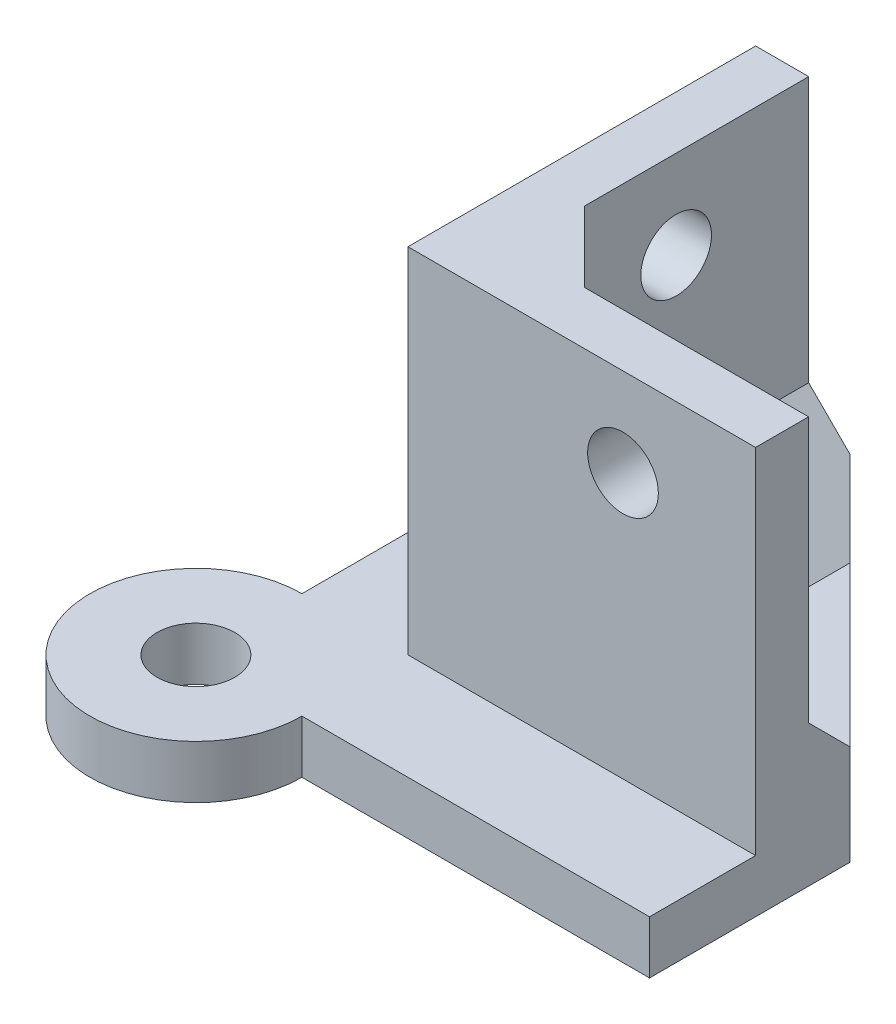
SolidWorks part; units mm, degrees
ref_plane "前视" through (0, 0, 0) normal (0, 0, 1) x (1, 0, 0)
ref_plane "上视" through (0, 0, 0) normal (0, 1, 0) x (1, 0, 0)
ref_plane "右视" through (0, 0, 0) normal (1, 0, 0) x (0, 0, -1)
sketch "Sketch1" plane through (0, 0, 0) normal (0, 1, 0) x (1, 0, 0)
  line L0 (0, 0) -> (0, 19)
  line L1 (0, 0) -> (19, 0)
  line L2 (19, 0) -> (0, 19)
  dimension "D1" = 19
  dimension "D2" = 19
extrude "Boss-Extrude1" add sketch "Sketch1" along normal blind 5
sketch "Sketch2" plane through (0, 5, 0) normal (0, 1, 0) x (1, 0, 0)
  line L0 (0, 19) -> (0, 0)
  line L1 (0, 0) -> (19, 0)
  line L2 (19, 0) -> (16, 3)
  line L3 (19, 0) -> (0, 19) construction
  line L4 (16, 3) -> (3, 3)
  line L5 (3, 3) -> (3, 16)
  line L6 (3, 16) -> (0, 19)
  dimension "D1" = 3
  dimension "D2" = 3
extrude "Boss-Extrude2" add sketch "Sketch2" along normal blind 15
sketch "Sketch3" plane through (0, 0, 0) normal (0, 0, 1) x (1, 0, 0)
  line L0 (0, 20) -> (0, 0) construction
  line L1 (0, 0) -> (19, 0) construction
  circle A0 centre (11.5, 15) radius 2
  dimension "D1" = 11.5
  dimension "D2" = 15
extrude "Cut-Extrude1" cut sketch "Sketch3" against normal through all
sketch "Sketch4" plane through (0, 0, 0) normal (-1, 0, 0) x (0, 0, 1)
  line L0 (-19, 0) -> (0, 0) construction
  line L1 (0, 20) -> (0, 0) construction
  circle A0 centre (-11.5, 15) radius 2
  dimension "D1" = 15
  dimension "D2" = 11.5
extrude "Cut-Extrude2" cut sketch "Sketch4" against normal through all
fillet "Fillet1" radius 1 6 edges at (9.5, 20, -3) (3, 20, -9.5) (1.5, 20, -17.5) (17.5, 20, -1.5) (19, 10, 0) (0, 10, -19)
sketch "Sketch5" plane through (0, 0, 0) normal (0, -1, 0) x (1, 0, 0)
  line L0 (28, 9) -> (-9, 9)
  line L1 (-9, 9) -> (-9, -28)
  line L3 (1.7071, -17.2929) -> (17.2929, -1.7071)
  line L4 (16.5858, 0) -> (0, 0)
  line L5 (0, 0) -> (0, -16.5858)
  line L6 (-9, -28) -> (28, 9)
  line L7 (0, 0) -> (16.5858, 0) construction
  line L8 (0, -16.5858) -> (0, 0) construction
  arc A2 (17.2929, -1.7071) -> (16.5858, 0) centre (16.5858, -1) ccw
  arc A3 (0, -16.5858) -> (1.7071, -17.2929) centre (1, -16.5858) ccw
  dimension "D2" = 9
  dimension "D3" = 9
  dimension "D1" = 0
extrude "Boss-Extrude3" add sketch "Sketch5" along normal blind 2.4
sketch "Sketch6" plane through (0, 0, 0) normal (0, 1, 0) x (1, 0, 0)
  line L0 (-9, -9) -> (-9, 28) construction
  line L1 (28, -9) -> (-9, -9) construction
  line L2 (-9, -9) -> (-9, 16.6732)
  line L3 (16.6669, -6) -> (16.6669, -9)
  line L4 (-6, 16.6732) -> (-9, 16.6732)
  line L5 (28, -6) -> (-6, -6)
  line L6 (-6, -6) -> (-6, 28)
  line L7 (16.6669, -6) -> (-6, -6)
  line L8 (-6, -6) -> (-6, 16.6732)
  line L9 (16.6669, -9) -> (-9, -9)
  dimension "D1" = 3
extrude "Boss-Extrude4" add sketch "Sketch6" along normal blind 20
sketch "Sketch7" plane through (0, 0, 9) normal (0, 0, 1) x (1, 0, 0)
  circle A0 centre (11.5, 15) radius 2 construction
  circle A1 centre (11.5, 15) radius 2
extrude "Cut-Extrude3" cut sketch "Sketch7" against normal through all both and the other way through all
sketch "Sketch8" plane through (-9, 0, 0) normal (-1, 0, 0) x (0, 0, 1)
  circle A0 centre (-11.5, 15) radius 2 construction
  circle A1 centre (-11.5, 15) radius 2
extrude "Cut-Extrude4" cut sketch "Sketch8" against normal through all both and the other way through all
sketch "Sketch9" plane through (0, 0, 0) normal (0, 1, 0) x (1, 0, 0)
  line L0 (16.6669, -9) -> (16.6669, -6) construction
  line L1 (-6, 16.6732) -> (-9, 16.6732) construction
  line L2 (-9, 16.6732) -> (-9, 28) construction
  line L3 (-9, 28) -> (1.7071, 17.2929) construction
  line L4 (28, -9) -> (16.6669, -9) construction
  line L5 (17.2929, 1.7071) -> (28, -9) construction
  line L6 (16.6669, -9) -> (16.6669, 2.3331)
  line L7 (2.3268, 16.6732) -> (-9, 16.6732)
  line L8 (-9, 16.6732) -> (-9, 28)
  line L9 (-9, 28) -> (17.2929, 1.7071)
  line L10 (28, -9) -> (16.6669, -9)
  line L11 (17.2929, 1.7071) -> (28, -9)
  line M2 (16.6669, -6) -> (16.6669, -9)
  line M3 (16.6669, -9) -> (28, -9)
  line M4 (28, -9) -> (17.2929, 1.7071)
  arc M5 (17.2929, 1.7071) -> (16.5858, 0) centre (16.5858, 1) cw
  arc M8 (0, 16.5858) -> (1.7071, 17.2929) centre (1, 16.5858) cw
  line M9 (1.7071, 17.2929) -> (-9, 28)
  line M10 (-9, 28) -> (-9, 16.6732)
  line M11 (-9, 16.6732) -> (-6, 16.6732)
extrude "Cut-Extrude5" cut sketch "Sketch9" against normal blind 20 contours L6 M2 M3 M4 M5 | L7 M8 M9 M10 M11 region at (20.5251, 0, 5.371) region at (-5.3718, 0, -20.5287)
sketch "Sketch10" plane through (0, 0, 0) normal (0, 1, 0) x (1, 0, 0)
  line L2 (1.7071, 17.2929) -> (17.2929, 1.7071) construction
  line L3 (0, 16.5858) -> (0, 0) construction
  line L4 (0, 0) -> (16.5858, 0) construction
  line L5 (1.7071, 17.2929) -> (17.2929, 1.7071)
  line L6 (0, 16.5858) -> (0, 0)
  line L7 (0, 0) -> (16.5858, 0)
  arc A2 (1.7071, 17.2929) -> (0.0038, 16.6732) centre (1, 16.5858) ccw construction
  arc A3 (16.6669, 0.0033) -> (17.2929, 1.7071) centre (16.5858, 1) ccw construction
  arc A4 (1.7071, 17.2929) -> (0, 16.5858) centre (1, 16.5858) ccw
  arc A5 (16.5858, 0) -> (17.2929, 1.7071) centre (16.5858, 1) ccw
extrude "Cut-Extrude6" cut sketch "Sketch10" along normal through all
sketch "Sketch11" plane through (0, 0, 0) normal (0, 1, 0) x (1, 0, 0)
  line L0 (0.0038, 16.6732) -> (-6, 16.6732) construction
  line L1 (17.2929, 1.7071) -> (1.7071, 17.2929) construction
  line L2 (16.6669, -9) -> (16.6669, 0.0033) construction
  line L3 (2.3268, 16.6732) -> (0.0038, 16.6732)
  line L4 (17.2929, 1.7071) -> (16.6669, 2.3331)
  line L5 (16.6669, 0.0033) -> (16.6669, 2.3331)
  line L6 (2.3268, 16.6732) -> (1.7071, 17.2929)
  arc A0 (1.7071, 17.2929) -> (0.0038, 16.6732) centre (1, 16.5858) ccw construction
  arc A1 (16.6669, 0.0033) -> (17.2929, 1.7071) centre (16.5858, 1) ccw construction
  arc A2 (1.7071, 17.2929) -> (0.0038, 16.6732) centre (1, 16.5858) ccw
  arc A3 (16.6669, 0.0033) -> (17.2929, 1.7071) centre (16.5858, 1) ccw
extrude "Cut-Extrude7" cut sketch "Sketch11" against normal through all
sketch "Sketch12" plane through (0, -2.4, 0) normal (0, -1, 0) x (1, 0, 0)
  circle A0 centre (-9, 9) radius 6
extrude "Boss-Extrude5" add sketch "Sketch12" against normal blind 2.4
sketch "Sketch13" plane through (0, 0, 0) normal (0, 1, 0) x (1, 0, 0)
  circle A0 centre (-9, -9) radius 2.2
extrude "Cut-Extrude8" cut sketch "Sketch13" against normal through all both and the other way through all
sketch "Sketch14" plane through (0, 0, 0) normal (0, 1, 0) x (1, 0, 0)
  circle A1 centre (-9, -9) radius 4
extrude "Cut-Extrude9" cut sketch "Sketch14" along normal through all
sketch "Sketch15" plane through (0, 0, 0) normal (0, 1, 0) x (1, 0, 0)
  line L0 (-9, -5) -> (-5, -5)
  line L1 (-5, -9) -> (-5, -5)
  arc A0 (-5, -9) -> (-9, -5) centre (-9, -9) ccw construction
  arc A1 (-5, -9) -> (-9, -5) centre (-9, -9) ccw
extrude "Cut-Extrude10" cut sketch "Sketch15" along normal through all
sketch "Sketch16" plane through (0, 0, 0) normal (0, 1, 0) x (1, 0, 0)
  line L1 (0, 16.6732) -> (-3, 16.6732)
  line L2 (0, 16.6732) -> (0, 4)
  line L3 (0, -3) -> (-3, -3)
  line L4 (-3, 16.6732) -> (-3, -3)
  line L5 (-9, 16.6732) -> (-9, -5) construction
  line L6 (0, -3) -> (16.6669, -3)
  line L7 (4, 0) -> (0, 4)
  line L8 (16.6669, -3) -> (16.6669, 0)
  line L9 (4, 0) -> (16.6669, 0)
  line L10 (16.6669, -6) -> (16.6669, 2.3331) construction
  line L11 (-5, -9) -> (16.6669, -9) construction
  dimension "D1" = 6
  dimension "D2" = 3
  dimension "D3" = 3
  dimension "D4" = 6
  dimension "D5" = 45
  dimension "D6" = 4
extrude "Boss-Extrude6" add sketch "Sketch16" along normal up to surface (20 mm away) up to face at (-7.5, 20, -5.8366)
sketch "Sketch17" plane through (0, 0, 0) normal (1, 0, 0) x (0, 0, -1)
  line L0 (16.6732, 20) -> (16.6732, 0) construction
  line L1 (4, 0) -> (16.6732, 0) construction
  circle A1 centre (9.1732, 15) radius 2
  dimension "D1" = 7.5
  dimension "D2" = 15
extrude "Cut-Extrude11" cut sketch "Sketch17" against normal through all
sketch "Sketch18" plane through (0, 0, 3) normal (0, 0, 1) x (1, 0, 0)
  line L1 (16.6669, 0) -> (4, 0) construction
  line L3 (16.6669, 20) -> (16.6669, -2.4) construction
  circle A1 centre (9.1669, 15) radius 2
  dimension "D1" = 7.5
  dimension "D2" = 15
extrude "Cut-Extrude12" cut sketch "Sketch18" against normal through all
sketch "Sketch19" plane through (0, 0, 0) normal (0, 1, 0) x (1, 0, 0)
  line L0 (-9, -5) -> (-6, -5) construction
  line L1 (-6, -5) -> (-6, 16.6732) construction
  line L2 (-6, 16.6732) -> (-9, 16.6732) construction
  line L3 (-9, 16.6732) -> (-9, -5) construction
  line L4 (-5, -6) -> (-5, -9) construction
  line L5 (-5, -9) -> (16.6669, -9) construction
  line L6 (16.6669, -9) -> (16.6669, -6) construction
  line L7 (16.6669, -6) -> (-5, -6) construction
  line L8 (-9, -5) -> (-6, -5)
  line L9 (-6, -5) -> (-6, 16.6732)
  line L10 (-6, 16.6732) -> (-9, 16.6732)
  line L11 (-9, 16.6732) -> (-9, -5)
  line L12 (-5, -6) -> (-5, -9)
  line L13 (-5, -9) -> (16.6669, -9)
  line L14 (16.6669, -9) -> (16.6669, -6)
  line L15 (16.6669, -6) -> (-5, -6)
extrude "Cut-Extrude13" cut sketch "Sketch19" along normal through all
chamfer "Chamfer1" distance 5 angle 45 3 edges at (0, 0, -10.3366) (2, 0, -2) (10.3334, 0, 0)
sketch "Sketch20" plane through (0, -2.4, 0) normal (0, -1, 0) x (1, 0, 0)
  line L5 (16.6669, 9) -> (-3, 9)
  line L6 (-9, 3) -> (-9, -16.6732)
  line L7 (-9, -16.6732) -> (2.3268, -16.6732)
  line L8 (2.3268, -16.6732) -> (16.6669, -2.3331)
  line L9 (16.6669, -2.3331) -> (16.6669, 9)
  line L10 (16.6669, 9) -> (-3, 9)
  line L11 (-9, 3) -> (-9, -16.6732)
  line L12 (-9, -16.6732) -> (2.3268, -16.6732)
  line L13 (2.3268, -16.6732) -> (16.6669, -2.3331)
  line L14 (16.6669, -2.3331) -> (16.6669, 9)
  circle A0 centre (-9, 9) radius 2.2 construction
  arc A1 (-3, 9) -> (-9, 3) centre (-9, 9) ccw
  arc A2 (-3, 9) -> (-9, 3) centre (-9, 9) ccw
  circle A3 centre (-9, 9) radius 2.2
  dimension "D1" = 0
extrude "Boss-Extrude7" add sketch "Sketch20" along normal blind 0.6
